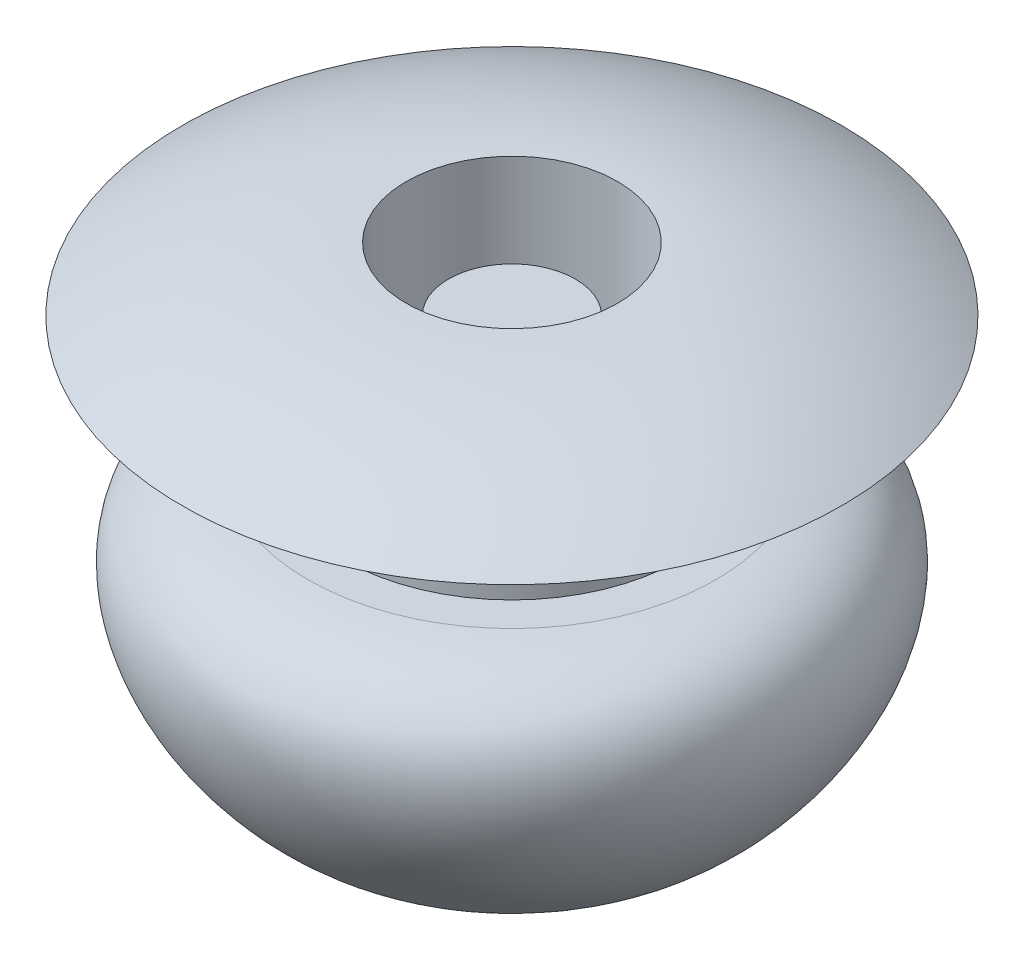
SolidWorks part; units mm, degrees
material "AISI 316 Stal nierdzewna odprężona (SS)"
ref_plane "Płaszczyzna przednia" through (0, 0, 0) normal (0, 0, 1) x (1, 0, 0)
ref_plane "Płaszczyzna górna" through (0, 0, 0) normal (0, 1, 0) x (1, 0, 0)
ref_plane "Płaszczyzna prawa" through (0, 0, 0) normal (1, 0, 0) x (0, 0, -1)
sketch "Szkic1" plane through (0, 0, 0) normal (1, 0, 0) x (0, 0, -1)
  line L1 (0, 0) -> (-0.75, 0)
  line L2 (-0.75, 0) -> (-0.75, -1.7007)
  line L3 (-0.75, -1.7007) -> (-1.25, -1.7007)
  line L4 (-1.25, -1.7007) -> (-1.25, 0.75)
  line L5 (-3.9, 0) -> (-2, 0)
  line L6 (-2, 0) -> (-2, -1.5)
  line L7 (-2, -1.5) -> (-2.4139, -1.5)
  line L8 (0, 0) -> (0, 0.4842) construction
  line L9 (0, -1.7007) -> (0, 0)
  line L10 (0, -1.7007) -> (0, -3.2007)
  line L11 (64.7945, -1.5) -> (68.7945, -1.5) construction
  arc A0 (-1.25, 0.75) -> (-3.9, 0) centre (-1.25, -4.3067) ccw
  ellipse E0 centre (0, -2.4507) end of major axis (-1.75, -2.4507) minor radius 0.75 (-0.956, -3.0789) -> (0, -3.2007) ccw
  spline S0 degree 3 poles (-2.4139, -1.5) (-3.8675, -1.6697) (-3.5289, -3.802) (-1.084, -5.3735) (-0.2718, -3.3749) (-0.956, -3.0789) knots 0 0 0 0 0.464993 0.721928 1 1 1 1
  dimension "D1" = 7.8
  dimension "D2" = 2.5
  dimension "D3" = 4
  dimension "D4" = 0.75
  dimension "D5" = 1.5
  dimension "D6" = 1.5
  dimension "D7" = 3.5
  dimension "D8" = 3.1855
  dimension "D9" = 2.5026
  dimension "D10" = 1.9
  dimension "D11" = 1.5789
  dimension "D12" = 0.5792
  dimension "D13" = 4.8278
  dimension "D14" = 3.3858
  dimension "D15" = 2.8395
  dimension "D16" = 1.25
  dimension "D17" = 0.6409
  dimension "D18" = 0.956
revolve "Obrót1" add sketch "Szkic1" angle 360 about L8
